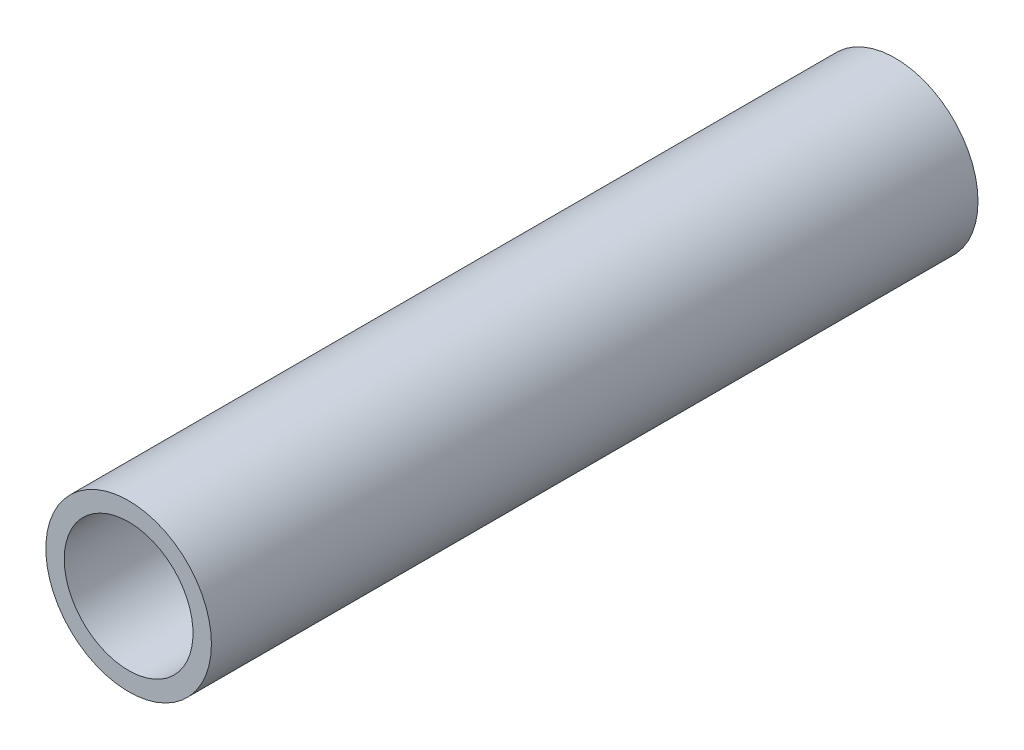
SolidWorks part; units mm, degrees
material "Plain Carbon Steel"
ref_plane "Front" through (0, 0, 0) normal (0, 0, 1) x (1, 0, 0)
ref_plane "Top" through (0, 0, 0) normal (0, 1, 0) x (1, 0, 0)
ref_plane "Right" through (0, 0, 0) normal (1, 0, 0) x (0, 0, -1)
sketch "Sketch1" plane through (0, 0, 0) normal (0, 0, 1) x (1, 0, 0)
  circle A0 centre (-7.3192, 4.997) radius 13.716
  dimension "D1" = 27.432
extrude "Boss-Extrude1" add sketch "Sketch1" along normal blind 127
sketch "Sketch2" plane through (0, 0, 0) normal (0, 0, -1) x (-1, 0, 0)
  circle A0 centre (7.3192, 4.997) radius 10.668
  dimension "D1" = 21.336
extrude "Cut-Extrude1" cut sketch "Sketch2" against normal blind 127
